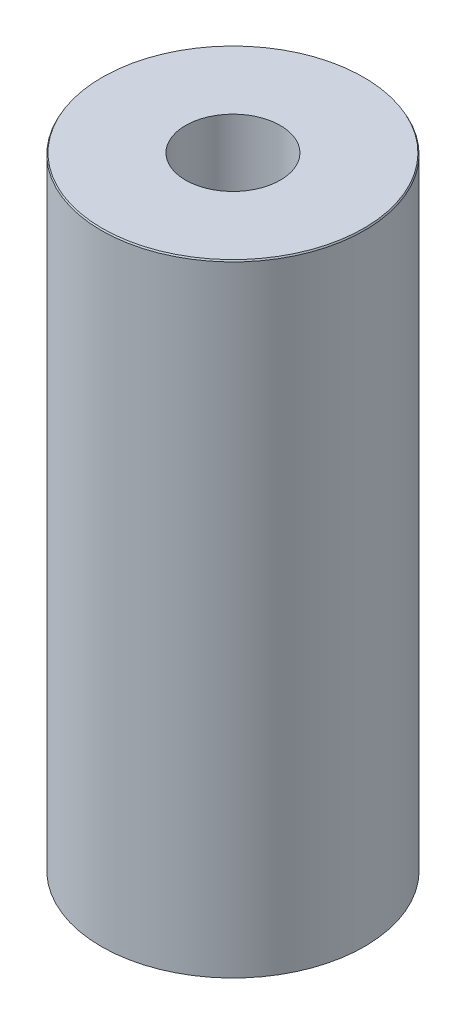
SolidWorks part; units mm, degrees
ref_plane "Front Plane" through (0, 0, 0) normal (0, 0, 1) x (1, 0, 0)
ref_plane "Top Plane" through (0, 0, 0) normal (0, 1, 0) x (1, 0, 0)
ref_plane "Right Plane" through (0, 0, 0) normal (1, 0, 0) x (0, 0, -1)
sketch "Sketch1" plane through (0, 0, 0) normal (0, 1, 0) x (1, 0, 0)
  circle A0 centre (0, 0) radius 47.5
  dimension "SHAFT_OD" = 95
extrude "Boss-Extrude1" add sketch "Sketch1" along normal blind 224.5919
sketch "Sketch2" plane through (0, 0, 0) normal (0, 1, 0) x (1, 0, 0)
  circle A0 centre (0, 0) radius 17.1057
  dimension "BORE_D" = 34.2114
extrude "Cut-Extrude1" cut sketch "Sketch2" along normal through all
chamfer "Chamfer1" distance 0.5163 angle 30 2 edges at (0, 224.5919, 47.5) (0, 0, 47.5) first distance on face at (0, 224.5919, 47.5) first distance on face at (0, 0, 17.1057)
